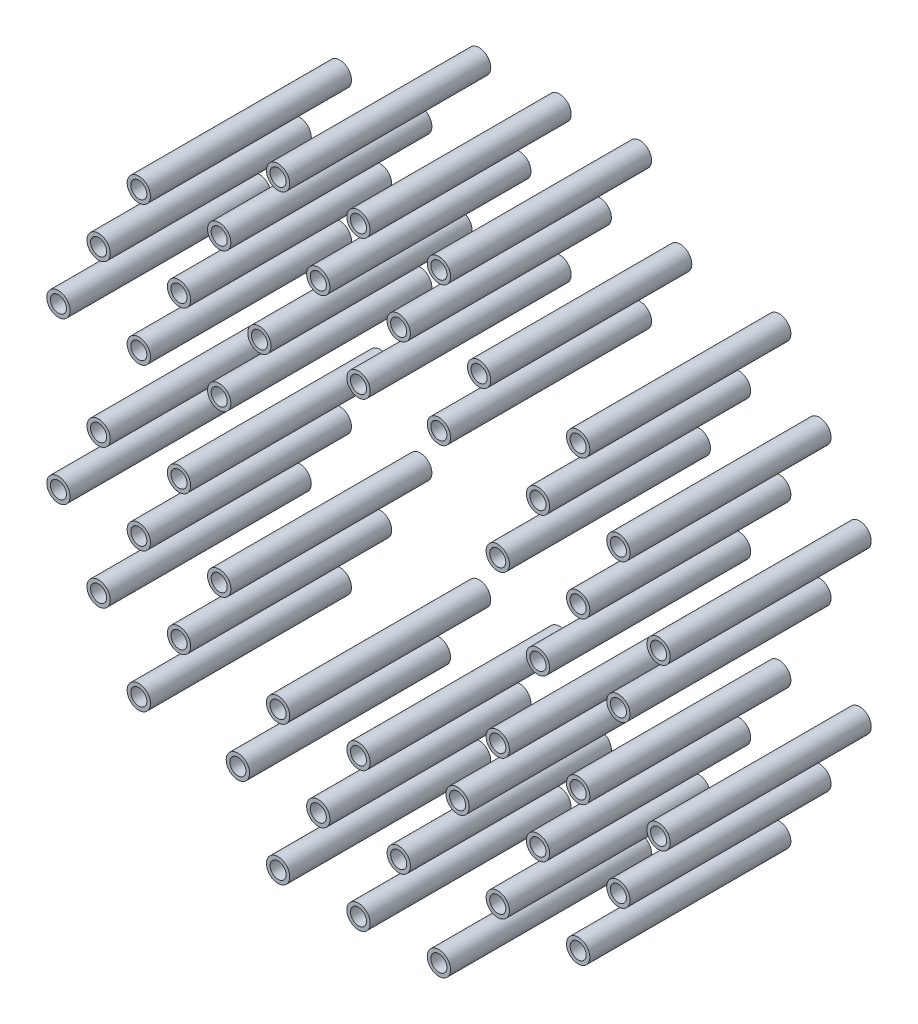
SolidWorks part; units mm, degrees
ref_plane "Front Plane" through (0, 0, 0) normal (0, 0, 1) x (1, 0, 0)
ref_plane "Top Plane" through (0, 0, 0) normal (0, 1, 0) x (1, 0, 0)
ref_plane "Right Plane" through (0, 0, 0) normal (1, 0, 0) x (0, 0, -1)
sketch "Sketch1" plane through (0, 0, 0) normal (0, 0, 1) x (1, 0, 0)
  line L0 (0, 10.16) -> (-2.54, 14.5594) construction
  line L1 (-2.54, 14.5594) -> (2.54, 14.5594) construction
  line L2 (2.54, 14.5594) -> (0, 10.16) construction
  line L3 (2.54, 14.5594) -> (0, 18.9588) construction
  line L4 (0, 18.9588) -> (-2.54, 14.5594) construction
  line L5 (-2.54, 14.5594) -> (-5.08, 18.9588) construction
  line L6 (-5.08, 18.9588) -> (0, 18.9588) construction
  line L7 (0, 10.16) -> (5.08, 10.16) construction
  line L8 (5.08, 10.16) -> (2.54, 14.5594) construction
  line L9 (2.54, 14.5594) -> (7.62, 14.5594) construction
  line L10 (7.62, 14.5594) -> (5.08, 10.16) construction
  line L11 (2.54, 14.5594) -> (5.08, 18.9588) construction
  line L12 (5.08, 18.9588) -> (0, 18.9588) construction
  line L13 (7.62, 14.5594) -> (5.08, 18.9588) construction
  line L14 (0, 10.16) -> (0, 0) construction
  circle A0 centre (0, 10.16) radius 0.7366
  circle A1 centre (0, 10.16) radius 0.508
  circle A2 centre (5.08, 10.16) radius 0.7366
  circle A3 centre (5.08, 10.16) radius 0.508
  circle A4 centre (7.62, 14.5594) radius 0.7366
  circle A5 centre (7.62, 14.5594) radius 0.508
  circle A6 centre (2.54, 14.5594) radius 0.7366
  circle A7 centre (2.54, 14.5594) radius 0.508
  circle A8 centre (-2.54, 14.5594) radius 0.7366
  circle A9 centre (-2.54, 14.5594) radius 0.508
  circle A10 centre (0, 18.9588) radius 0.7366
  circle A11 centre (0, 18.9588) radius 0.508
  circle A12 centre (5.08, 18.9588) radius 0.7366
  circle A13 centre (5.08, 18.9588) radius 0.508
  circle A14 centre (-5.08, 18.9588) radius 0.7366
  circle A15 centre (-5.08, 18.9588) radius 0.508
  dimension "Injector Needles Inner Diameter" = 1.016
  dimension "Injector Needles Outer Diameter" = 1.4732
  dimension "Distance Between Needles" = 5.08
  dimension "1st Hole Distance From Center" = 10.16
extrude "Boss-Extrude1" add sketch "Sketch1" along normal blind 12.7
ref_axis "Axis1" through (0, 0, 13.335) along (0, 0, -1)
pattern_circular "CirPattern2" count 6 over 360 about axis through (0, 0, 13.335) along (0, 0, -1) of bodies 108 107 106 105 104 103 102 101
